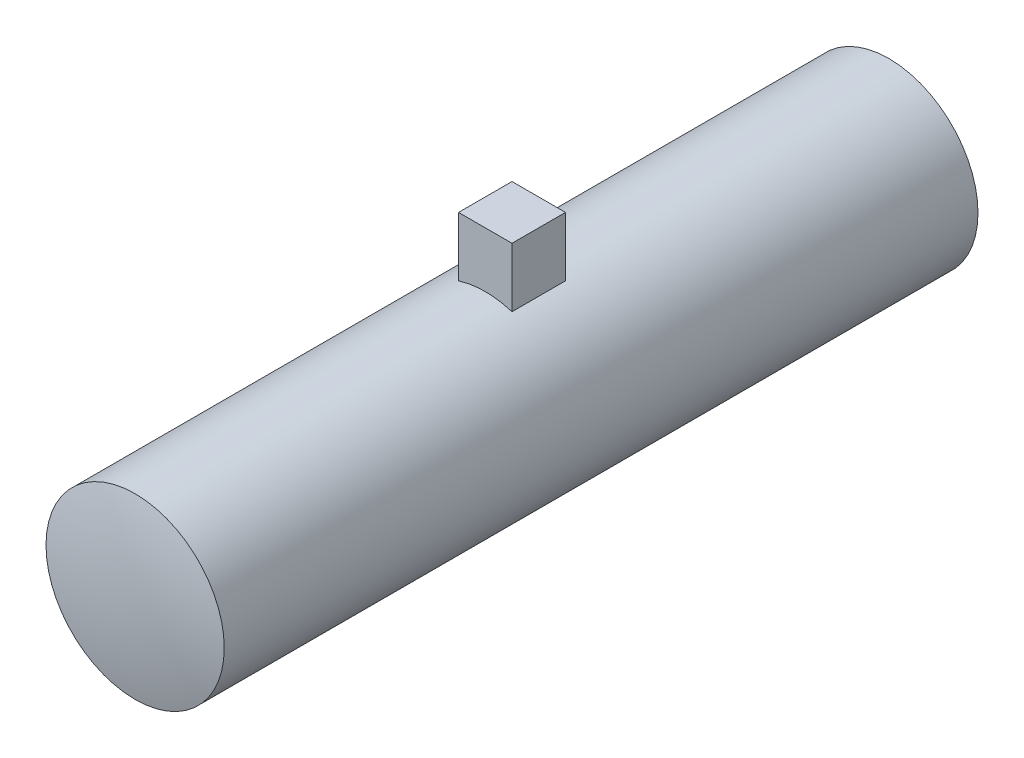
SolidWorks part; units mm, degrees
ref_plane "Front Plane" through (0, 0, 0) normal (0, 0, 1) x (1, 0, 0)
ref_plane "Top Plane" through (0, 0, 0) normal (0, 1, 0) x (1, 0, 0)
ref_plane "Right Plane" through (0, 0, 0) normal (1, 0, 0) x (0, 0, -1)
sketch "Sketch4" plane through (0, 0, 0) normal (0, 0, 1) x (1, 0, 0)
  line L0 (118.2783, 361.3249) -> (982.8327, 361.3249) construction
  line L1 (0, 0) -> (0, 70)
  line L2 (0, 70) -> (-2, 70)
  line L3 (-2, 70) -> (-2, 0)
  line L4 (-2, 0) -> (0, 0)
  line L5 (0, 0) -> (14, 0)
  line L6 (12.4732, 68.0138) -> (14.4732, 68.0138)
  line L7 (9, 0) -> (15, 0)
  line L8 (7, 0) -> (12.4732, 68.0138)
  line L10 (9, 0) -> (14.4732, 68.0138)
  line L11 (-2, 0) -> (-9, 0)
  line L12 (-9, 0) -> (-11, 0)
  line L13 (-11, 0) -> (-18, 0)
  line L14 (-18, 0) -> (-20, 0)
  line L15 (-11, 0) -> (-17.4559, 67.3971)
  line L16 (-17.4559, 67.3971) -> (-15.4559, 67.3971)
  line L17 (-15.4559, 67.3971) -> (-9, 0)
  line L18 (-18, 0) -> (-26.2108, 62.7795)
  line L19 (-26.2108, 62.7795) -> (-28.2108, 62.7795)
  line L20 (-28.2108, 62.7795) -> (-20, 0)
  line L21 (-20, 0) -> (-26, 0)
  line L22 (0, 65) -> (-20, 65)
  line L24 (0, 55) -> (20.8335, 55)
  line L26 (0, 50) -> (-31.2148, 50)
  line L27 (-26, 0) -> (15, 0)
  line L28 (-26, 0) -> (-26, -2)
  line L29 (-26, -2) -> (15, -2)
  line L30 (15, 0) -> (15, -2)
  dimension "D1" = 70
  dimension "D2" = 2
  dimension "D3" = 14
  dimension "D4" = 2
  dimension "D5" = 2
  dimension "D6" = 7
  dimension "D7" = 2
  dimension "D8" = 7
  dimension "D9" = 2
  dimension "D10" = 2
  dimension "D11" = 2
  dimension "D12" = 70
  dimension "D13" = 65
  dimension "D14" = 10
  dimension "D15" = 5
  dimension "D16" = 6
  dimension "D17" = 6
  dimension "D18" = 2
extrude "Boss-Extrude1" add sketch "Sketch4" along normal blind 2 contours L24 L8 L5 L10 | L1 L26 L3 L4 | L17 L26 L15 L12 | L18 L26 L20 L14 | L30 L7 L5 L4 L11 L12 L13 L14 L21 L28 L29 | L26 L17 L22 L15 | L26 L1 L22 L3 region at (-1, 25, 0) region at (-5.5, -1, 0) region at (-1, 57.5, 0) region at (10.213, 27.5, 0) region at (-12.3947, 25, 0) region at (-15.5079, 57.5, 0) region at (-22.2697, 25, 0)
sketch "Sketch5" plane through (0, 0, 2) normal (0, 0, 1) x (1, 0, 0)
  line L0 (7, 0) -> (11.4117, 54.8228)
  line L1 (7, 0) -> (11.426, 55) construction
  line L2 (11.4117, 54.8228) -> (21.9246, 53.9768)
  line L3 (9, 0) -> (13.3988, 54.6629)
  line L4 (9, 0) -> (13.426, 55) construction
  line L5 (-2, 0) -> (-2, 65)
  line L6 (-2, 65) -> (0, 65)
  line L7 (0, 65) -> (0, 0)
  line L8 (-9, 0) -> (-15.1979, 64.7038)
  line L9 (-15.2263, 65) -> (-9, 0) construction
  line L10 (-15.1979, 64.7038) -> (-10.585, 65.1457)
  line L11 (-24.4842, 49.5778) -> (-21.0999, 50.0204)
  line L12 (-10.585, 65.1457) -> (-20.2054, 64.2242)
  line L13 (-11, 0) -> (-17.1797, 64.514)
  line L14 (-11, 0) -> (-17.2263, 65) construction
  line L15 (-18, 0) -> (-24.4842, 49.5778)
  line L16 (-18, 0) -> (-24.5394, 50) construction
  line L17 (-21.0999, 50.0204) -> (-29.0833, 48.9763)
  line L18 (-20, 0) -> (-26.4506, 49.3206)
  line L20 (-24.4842, 55.6866) -> (-21.0999, 50.0204)
  line L23 (11.4117, 54.8228) -> (9.3756, 55.8722)
  line L25 (22.6925, 57.6139) -> (21.9246, 53.9768)
  line L26 (-10.585, 65.1457) -> (2.5876, 67.2021)
  line L27 (2.5876, 67.2021) -> (9.3756, 55.8722)
  line L28 (22.6925, 57.6139) -> (5.5245, 72.3941)
  line L29 (5.5245, 72.3941) -> (-16.3252, 68.1044)
  line L30 (-29.0833, 48.9763) -> (-29.6656, 62.8492)
  line L31 (-29.6656, 62.8492) -> (-16.3252, 68.1044)
  line L32 (-20.2054, 64.2242) -> (-24.4842, 55.6866)
  dimension "D1" = 55
  dimension "D2" = 90
  dimension "D3" = 65
  dimension "D4" = 90
  dimension "D5" = 50
  dimension "D6" = 90
extrude "Cut-Extrude4" cut sketch "Sketch5" against normal blind 10 contours L32 L12 L16 L14 L13 L10 L26 L27 L23 L3 L1 L2 L25 L28 L29 L31 L30 L17 L20 L18 L11 | L3 L2 L26 L1 | L12 L13 L14 L16 | L17 L18 L20 region at (10.6564, 55.8573, 2)
sketch "Sketch6" plane through (0, 0, 2) normal (0, 0, 1) x (1, 0, 0)
  line L0 (-24.4842, 49.5778) -> (-22.6038, 35.2002)
  line L1 (-18, 0) -> (-24.4842, 49.5778) construction
  line L2 (-15.1979, 64.7038) -> (-13.8153, 50.2699)
  line L3 (-15.1979, 64.7038) -> (-9, 0) construction
  line L4 (-2, 65) -> (-2, 50.5)
  line L5 (-2, 65) -> (-2, 0) construction
  line L6 (11.4117, 54.8228) -> (10.2486, 40.3695)
  line L7 (7, 0) -> (11.4117, 54.8228) construction
  line L8 (10.2486, 40.3695) -> (13.4056, 40.1154)
  line L9 (13.4056, 40.1154) -> (14.5687, 54.5687)
  line L10 (14.5687, 54.5687) -> (11.4117, 54.8228)
  line L11 (-2, 50.5) -> (0, 50.5)
  line L12 (0, 0) -> (0, 65) construction
  line L13 (0, 50.5) -> (0, 65)
  line L14 (0, 65) -> (-2, 65)
  line L15 (-15.1979, 64.7038) -> (-17.1797, 64.514)
  line L16 (-17.1797, 64.514) -> (-15.8153, 50.2699)
  line L17 (-11, 0) -> (-17.1797, 64.514) construction
  line L18 (-13.8153, 50.2699) -> (-15.7971, 50.0801)
  line L19 (-15.7971, 50.0801) -> (-16.1419, 53.6796)
  line L20 (-22.6038, 35.2002) -> (-24.5702, 34.943)
  line L21 (-26.4506, 49.3206) -> (-20, 0) construction
  line L22 (-24.5702, 34.943) -> (-26.4506, 49.3206)
  line L23 (-26.4506, 49.3206) -> (-24.4842, 49.5778)
  line L24 (-24.5702, 34.943) -> (-22.6038, 35.2002)
  line L25 (-24.4842, 49.5778) -> (-26.4506, 49.3206)
  line L26 (-24.5702, 34.943) -> (-26.4506, 49.3206)
  line M5 (-9, 0) -> (-15.1979, 64.7038)
  line M6 (-15.1979, 64.7038) -> (-17.1797, 64.514)
  line M7 (-17.1797, 64.514) -> (-11, 0)
  line M9 (-18, 0) -> (-24.4842, 49.5778)
  line M10 (-24.4842, 49.5778) -> (-26.4506, 49.3206)
  line M11 (-26.4506, 49.3206) -> (-20, 0)
  line M17 (9, 0) -> (13.3988, 54.6629)
  line M18 (13.3988, 54.6629) -> (11.4117, 54.8228)
  line M19 (11.4117, 54.8228) -> (7, 0)
  line M21 (0, 0) -> (0, 65)
  line M22 (0, 65) -> (-2, 65)
  line M23 (-2, 65) -> (-2, 0)
  dimension "D1" = 14.5
  dimension "D2" = 14.5
  dimension "D3" = 14.5
  dimension "D4" = 14.5
extrude "Cut-Extrude5" cut sketch "Sketch6" against normal blind 10 contours L8 M19 M17 M18 | L11 M23 M21 M22 | L18 L16 M5 M6 M7 | L20 M9 M10 M11 region at (-24.5272, 42.2604, 2) region at (-15.4975, 57.3919, 2) region at (-1, 57.75, 2) region at (11.8237, 47.5162, 2)
sketch "Sketch7" plane through (0, 50.5, 0) normal (0, 1, 0) x (1, 0, 0)
  line L0 (-1, 0) -> (-1, -2)
  line L1 (-2, 0) -> (0, 0) construction
  line L2 (-2, -2) -> (0, -2) construction
  line L5 (-7.25, 5.25) -> (5.25, 5.25)
  line L6 (-7.25, 5.25) -> (-7.25, -7.25)
  line L7 (-7.25, -7.25) -> (5.25, -7.25)
  line L8 (5.25, 5.25) -> (5.25, -7.25)
  line L9 (-7.25, 5.25) -> (5.25, -7.25) construction
  line L10 (-7.25, -7.25) -> (5.25, 5.25) construction
  point P7 (-1, -1)
  line M3 (-2, 0) -> (-2, -2)
  line M4 (-2, -2) -> (0, -2)
  line M5 (0, -2) -> (0, 0)
  line M6 (0, 0) -> (-2, 0)
  dimension "D1" = 12.5
  dimension "D2" = 12.5
extrude "Boss-Extrude2" add sketch "Sketch7" along normal blind 2.5 contours L8 L5 L6 L7 M3 M6 M5 M4 | L0 M6 M3 M4 | L0 M6 M4 M5 region at (-0.5, 50.5, 1) region at (-1.5, 50.5, 1) region at (-1, 50.5, -5.0732)
sketch "Sketch8" plane through (3.2936, 40.9292, 0) normal (0.0802, 0.9968, 0) x (0.9968, -0.0802, 0)
  line L0 (12.9774, 0) -> (10.9774, 0)
  line L1 (6.9774, 0) -> (12.9774, 0)
  line L2 (6.9774, 0) -> (6.9774, -2)
  line L3 (6.9774, -2) -> (12.9774, -2)
  line L4 (12.9774, 0) -> (12.9774, -2)
  line L5 (10.9774, 0) -> (10.9774, -2)
  dimension "D1" = 6
  dimension "D2" = 2
extrude "Boss-Extrude3" add sketch "Sketch8" against normal blind 41.5 contours L0 L5 L3 L4 region at (15.2325, 39.9684, 1)
sketch "Sketch9" plane through (0, 0, 2) normal (0, 0, 1) x (1, 0, 0)
  line L0 (7, 0) -> (9, 0)
  line L1 (9, 0) -> (12.2357, 40.2096)
  line L2 (12.2357, 40.2096) -> (10.2486, 40.3695)
  line L3 (10.2486, 40.3695) -> (7, 0)
extrude "Cut-Extrude6" cut sketch "Sketch9" against normal blind 41.5
sketch "Sketch10" plane through (-4.8971, 51.1242, 0) normal (-0.0954, 0.9954, 0) x (0.9954, 0.0954, 0)
  line L0 (-14.959, -2) -> (-12.959, -2)
  line L1 (-8.959, 0) -> (-14.959, 0)
  line L2 (-8.959, 0) -> (-8.959, -2)
  line L3 (-8.959, -2) -> (-14.959, -2)
  line L4 (-14.959, 0) -> (-14.959, -2)
  line L5 (-12.959, -2) -> (-12.959, 0)
  dimension "D1" = 6
  dimension "D2" = 2
extrude "Boss-Extrude4" add sketch "Sketch10" against normal blind 50.5 contours L0 L5 L1 L4 region at (-18.7925, 49.7931, 1)
sketch "Sketch11" plane through (0, 0, 2) normal (0, 0, 1) x (1, 0, 0)
  line L0 (-11, 0) -> (-9, 0)
  line L1 (-9, 0) -> (-13.8153, 50.2699)
  line L2 (-13.8153, 50.2699) -> (-15.7971, 50.0801)
  line L3 (-15.7971, 50.0801) -> (-11, 0)
extrude "Cut-Extrude7" cut sketch "Sketch11" against normal blind 50.5
sketch "Sketch12" plane through (3.2936, 40.9292, 0) normal (0.0802, 0.9968, 0) x (0.9968, -0.0802, 0)
  line L0 (11.9774, 0) -> (11.9774, -2)
  line L1 (12.9774, 0) -> (10.9774, 0) construction
  line L2 (10.9774, -2) -> (12.9774, -2) construction
  line L4 (5.7274, 5.25) -> (18.2274, 5.25)
  line L5 (5.7274, 5.25) -> (5.7274, -7.25)
  line L6 (5.7274, -7.25) -> (18.2274, -7.25)
  line L7 (18.2274, 5.25) -> (18.2274, -7.25)
  line L8 (5.7274, 5.25) -> (18.2274, -7.25) construction
  line L9 (5.7274, -7.25) -> (18.2274, 5.25) construction
  point P6 (11.9774, -1)
  line M3 (12.9774, 0) -> (10.9774, 0)
  line M4 (10.9774, 0) -> (10.9774, -2)
  line M5 (10.9774, -2) -> (12.9774, -2)
  line M6 (12.9774, -2) -> (12.9774, 0)
  dimension "D1" = 12.5
  dimension "D2" = 12.5
extrude "Boss-Extrude5" add sketch "Sketch12" along normal blind 2.5 contours L7 L4 L5 L6 M3 M6 M5 M4 | L0 M3 M5 M6 | L0 M3 M4 M5 region at (15.7309, 39.9283, 1) region at (14.7341, 40.0085, 1) region at (15.2325, 39.9684, -5.0732)
sketch "Sketch13" plane through (0, 0, 2) normal (0, 0, 1) x (1, 0, 0)
  line L0 (-5.5, -2) -> (-5.5, 50.5)
  line L1 (-26, -2) -> (15, -2) construction
  line L2 (-7.25, 50.5) -> (5.25, 50.5) construction
  line L3 (-17.7971, 49.8885) -> (-17.6064, 47.8976)
  line L4 (-13.0183, 0) -> (-17.7971, 49.8885) construction
  line L5 (-19.788, 49.6978) -> (-19.6155, 47.8976)
  line L6 (-15.0275, 0) -> (-19.788, 49.6978) construction
  line L7 (-19.788, 49.6978) -> (-17.7971, 49.8885)
  line L8 (-17.6064, 47.8976) -> (-19.5973, 47.7069)
  line L9 (-19.5973, 47.7069) -> (-19.6379, 48.1311)
  line M3 (-13.0183, 0) -> (-17.7971, 49.8885)
  line M4 (-17.7971, 49.8885) -> (-19.788, 49.6978)
  line M5 (-19.788, 49.6978) -> (-15.0275, 0)
  dimension "D1" = 2
extrude "Cut-Extrude8" cut sketch "Sketch13" against normal blind 2.5 and the other way through all contours L8 L5 M3 M4 M5 region at (-18.6972, 48.7977, 2)
sketch "Sketch14" plane through (-4.7064, 49.1333, 0) normal (-0.0954, 0.9954, 0) x (0.9954, 0.0954, 0)
  line L0 (-13.959, 0) -> (-13.959, -2)
  line L1 (-14.959, 0) -> (-12.959, 0) construction
  line L2 (-14.959, -2) -> (-12.959, -2) construction
  line L4 (-20.209, 5.25) -> (-7.709, 5.25)
  line L5 (-20.209, 5.25) -> (-20.209, -7.25)
  line L6 (-20.209, -7.25) -> (-7.709, -7.25)
  line L7 (-7.709, 5.25) -> (-7.709, -7.25)
  line L8 (-20.209, 5.25) -> (-7.709, -7.25) construction
  line L9 (-20.209, -7.25) -> (-7.709, 5.25) construction
  point P6 (-13.959, -1)
  line M3 (-14.959, -2) -> (-12.959, -2)
  line M4 (-12.959, -2) -> (-12.959, 0)
  line M5 (-12.959, 0) -> (-14.959, 0)
  line M6 (-14.959, 0) -> (-14.959, -2)
  dimension "D1" = 12.5
  dimension "D2" = 12.5
extrude "Boss-Extrude6" add sketch "Sketch14" along normal blind 2.5 contours L0 M5 M3 M4 | L0 M5 M6 M3 | L7 L4 L5 L6 M3 M6 M5 M4 region at (-18.1041, 47.8499, 1) region at (-19.0995, 47.7546, 1) region at (-18.6018, 47.8022, -5.0732)
sketch "Sketch15" plane through (-4.9065, 37.5148, 0) normal (-0.1297, 0.9916, 0) x (0.9916, 0.1297, 0)
  line L0 (-25.848, -2) -> (-23.848, -2)
  line L1 (-17.848, 0) -> (-25.848, 0)
  line L2 (-17.848, 0) -> (-17.848, -2)
  line L3 (-17.848, -2) -> (-25.848, -2)
  line L4 (-25.848, 0) -> (-25.848, -2)
  line L5 (-23.848, -2) -> (-23.848, 0)
  line L6 (-31.848, -2) -> (-29.848, -2)
  line L7 (-25.848, 0) -> (-31.848, 0)
  line L8 (-25.848, 0) -> (-25.848, -2)
  line L9 (-25.848, -2) -> (-31.848, -2)
  line L10 (-31.848, 0) -> (-31.848, -2)
  line L11 (-29.848, -2) -> (-29.848, 0)
  dimension "D1" = 8
  dimension "D2" = 2
  dimension "D3" = 6
  dimension "D4" = 2
extrude "Boss-Extrude7" add sketch "Sketch15" against normal blind 39.5 separate body contours L6 L11 L7 L10 region at (-35.494, 33.5143, 1)
sketch "Sketch16" plane through (-4.9065, 37.5148, 0) normal (-0.1297, 0.9916, 0) x (0.9916, 0.1297, 0)
  line L0 (-30.848, 0) -> (-30.848, -2)
  line L1 (-29.848, 0) -> (-31.848, 0) construction
  line L2 (-31.848, -2) -> (-29.848, -2) construction
  line L4 (-37.098, 5.25) -> (-24.598, 5.25)
  line L5 (-37.098, 5.25) -> (-37.098, -7.25)
  line L6 (-37.098, -7.25) -> (-24.598, -7.25)
  line L7 (-24.598, 5.25) -> (-24.598, -7.25)
  line L8 (-37.098, 5.25) -> (-24.598, -7.25) construction
  line L9 (-37.098, -7.25) -> (-24.598, 5.25) construction
  point P6 (-30.848, -1)
  line M3 (-31.848, -2) -> (-29.848, -2)
  line M4 (-29.848, -2) -> (-29.848, 0)
  line M5 (-29.848, 0) -> (-31.848, 0)
  line M6 (-31.848, 0) -> (-31.848, -2)
  dimension "D1" = 12.5
  dimension "D2" = 12.5
extrude "Boss-Extrude8" add sketch "Sketch16" along normal blind 2.5 contours L7 L4 L5 L6 M3 M6 M5 M4 | L0 M5 M3 M4 | L0 M5 M6 M3 region at (-34.9982, 33.5792, 1) region at (-35.9898, 33.4495, 1) region at (-35.494, 33.5143, -5.0732)
sketch "Sketch17" plane through (-5.2307, 39.9937, 0) normal (-0.1297, 0.9916, 0) x (0.9916, 0.1297, 0)
  line L0 (-37.098, -7.25) -> (-35.098, -7.25)
  line L1 (-37.098, 5.25) -> (-22.598, 5.25)
  line L2 (-37.098, 5.25) -> (-37.098, -7.25)
  line L3 (-37.098, -7.25) -> (-22.598, -7.25)
  line L4 (-22.598, 5.25) -> (-22.598, -7.25)
  line L5 (-35.098, -7.25) -> (-35.098, 5.25)
  line M2 (-24.598, -7.25) -> (-24.598, 5.25)
  dimension "D1" = 14.5
  dimension "D2" = 2
extrude "Boss-Extrude9" add sketch "Sketch17" against normal blind 2.5 contours L4 L1 L3 M2 region at (-28.6294, 36.9334, 1)
sketch "Sketch18" plane through (-5.2307, 39.9937, 0) normal (-0.1297, 0.9916, 0) x (0.9916, 0.1297, 0)
  line L0 (-37.098, -7.25) -> (-35.098, -7.25)
  line L2 (-35.098, -7.25) -> (-37.098, -7.25)
  line L3 (-35.098, -7.25) -> (-35.098, 5.25)
  line L4 (-35.098, 5.25) -> (-37.098, 5.25)
  line L5 (-37.098, -7.25) -> (-37.098, 5.25)
  line M2 (-37.098, -7.25) -> (-22.598, -7.25)
  line M4 (-22.598, 5.25) -> (-37.098, 5.25)
  line M5 (-37.098, 5.25) -> (-37.098, -7.25)
  dimension "D1" = 2
extrude "Cut-Extrude9" cut sketch "Sketch18" against normal blind 13.5 contours L3 M2 M4 M5 region at (-41.0239, 35.3124, 1)
sketch "Sketch19" plane through (-26, 0, 0) normal (-1, 0, 0) x (0, 0, 1)
  line L1 (0, 0) -> (2, 0)
  line L2 (0, 0) -> (0, -2)
  line L3 (0, -2) -> (2, -2)
  line L4 (2, 0) -> (2, -2)
extrude "Boss-Extrude10" add sketch "Sketch19" along normal blind 7.5
sketch "Sketch20" plane through (0, 0, 2) normal (0, 0, 1) x (1, 0, 0)
  line L0 (-31.8577, -2) -> (-29.8406, -2)
  line L1 (-29.8406, -2) -> (-29.3799, -5.5224)
  line L2 (-29.3799, -5.5224) -> (-31.363, -5.7818)
  line L3 (-31.363, -5.7818) -> (-31.8577, -2)
  line L4 (-20, 0) -> (-18, 0)
  line L5 (-18, 0) -> (-22.6038, 35.2002)
  line L6 (-22.6038, 35.2002) -> (-24.5702, 34.943)
  line L7 (-24.5702, 34.943) -> (-20, 0)
extrude "Cut-Extrude11" cut sketch "Sketch20" against normal blind 33.5
sketch "Sketch21" plane through (0, 0, 2) normal (0, 0, 1) x (1, 0, 0)
  line L0 (-36.4856, 33.3846) -> (-34.5025, 33.644)
  line L1 (-34.5025, 33.644) -> (-30.1022, 0)
  line L2 (-30.1022, 0) -> (-32.1192, 0)
  line L3 (-32.1192, 0) -> (-36.4856, 33.3846)
extrude "Cut-Extrude12" cut sketch "Sketch21" against normal blind 33.5
sketch "Sketch22" plane through (-4.9065, 37.5148, 0) normal (0.1297, -0.9916, 0) x (-0.9916, -0.1297, 0)
  line L0 (28.848, -7.25) -> (28.848, 5.25)
  line L1 (35.098, -7.25) -> (22.598, -7.25) construction
  line L2 (35.098, 5.25) -> (22.598, 5.25) construction
  line L3 (28.848, -1) -> (27.848, -1)
  line L4 (28.848, -1) -> (29.848, -1)
  line L5 (28.848, -1) -> (28.848, -2)
  line L6 (28.848, -1) -> (28.848, 0)
  line L8 (29.848, -1) -> (27.848, -1)
  line L9 (29.848, -1) -> (29.848, -2)
  line L10 (29.848, -2) -> (27.848, -2)
  line L11 (27.848, -1) -> (27.848, -2)
  line L12 (27.848, -1) -> (29.848, -1)
  line L13 (27.848, -1) -> (27.848, 0)
  line L14 (27.848, 0) -> (29.848, 0)
  line L15 (29.848, -1) -> (29.848, 0)
  dimension "D1" = 1
  dimension "D2" = 1
  dimension "D3" = 1
  dimension "D4" = 1
extrude "Boss-Extrude11" add sketch "Sketch22" along normal blind 35.5 contours L4 L15 L14 L0 | L10 L9 L4 L0 | L3 L11 L10 L0 | L14 L13 L3 L0 region at (-33.0151, 33.8385, 1.5) region at (-34.0067, 33.7088, 1.5) region at (-33.0151, 33.8385, 0.5) region at (-34.0067, 33.7088, 0.5)
sketch "Sketch24" plane through (18.1687, -1.4621, 0) normal (0.9968, -0.0802, 0) x (0, 0, -1)
  line L0 (-1, 41.0615) -> (-1, 55.5615)
  line L1 (5.25, 41.0615) -> (-7.25, 41.0615) construction
  line L2 (-1.7404, 43.5615) -> (-1.7404, 55.5615)
  line L3 (-7.25, 41.0615) -> (-1, 41.0615)
  line L4 (-7.25, 41.0615) -> (-7.25, 55.5615)
  line L6 (-1, 41.0615) -> (-1, 55.5615)
  line L8 (-1, 55.5615) -> (-1, 41.0615)
  line L9 (-1, 41.0615) -> (5.25, 41.0615)
  line L10 (5.25, 55.5615) -> (5.25, 41.0615)
  line L11 (5.25, 43.5615) -> (-7.25, 43.5615) construction
  line L12 (-7.25, 49.5615) -> (5.25, 49.5615)
  arc A1 (-7.25, 49.5615) -> (5.25, 49.5615) centre (-1, 49.282) cw
  point P17 (-1, 49.5615)
  line M4 (5.25, 43.5615) -> (-7.25, 43.5615)
  dimension "D1" = 14.5
extrude "Boss-Extrude13" add sketch "Sketch24" against normal blind 4 contours A1 L8 L12 | A1 L2 L12 L8 | A1 L12 L2 | L12 L4 L2 M4 | L12 L0 L10 M4 | L12 L2 L0 M4 region at (21.9035, 44.9494, 1.3702) region at (21.9035, 44.9494, -2.125) region at (22.3833, 50.9112, 1.3698) region at (22.3469, 50.459, -1.6268) region at (21.9035, 44.9494, 4.4952) region at (22.3404, 50.3778, 4.0322)
sketch "Sketch25" plane through (5.25, 0, 0) normal (1, 0, 0) x (0, 0, -1)
  line L0 (-1, 50.5) -> (-1, 65)
  line L1 (5.25, 50.5) -> (-7.25, 50.5) construction
  line L3 (-1, 65) -> (-7.25, 65)
  line L4 (-1, 65) -> (-1, 50.5)
  line L5 (-1, 50.5) -> (-7.25, 50.5)
  line L6 (-7.25, 65) -> (-7.25, 50.5)
  line L7 (-1, 65) -> (5.25, 65)
  line L8 (-1, 65) -> (-1, 50.5)
  line L9 (-1, 50.5) -> (5.25, 50.5)
  line L10 (5.25, 65) -> (5.25, 50.5)
  arc A0 (5.25, 57.75) -> (-7.25, 57.75) centre (-1, 58.681) ccw
  line M4 (5.25, 53) -> (-7.25, 53)
  dimension "D1" = 14.5
extrude "Boss-Extrude14" add sketch "Sketch25" against normal blind 4 contours L10 A0 L0 M4 | L0 A0 L6 M4 region at (5.25, 58.4301, 3.915) region at (5.25, 58.4301, -1.915)
sketch "Sketch26" plane through (-7.6739, -0.7351, 0) normal (0.9954, 0.0954, 0) x (0, 0, -1)
  line L0 (-1, 49.3582) -> (-1, 63.8582)
  line L1 (5.25, 49.3582) -> (-7.25, 49.3582) construction
  line L3 (-1, 63.8582) -> (-7.25, 63.8582)
  line L4 (-1, 63.8582) -> (-1, 49.3582)
  line L5 (-1, 49.3582) -> (-7.25, 49.3582)
  line L6 (-7.25, 63.8582) -> (-7.25, 49.3582)
  line L7 (-1, 63.8582) -> (5.25, 63.8582)
  line L8 (-1, 63.8582) -> (-1, 49.3582)
  line L9 (-1, 49.3582) -> (5.25, 49.3582)
  line L10 (5.25, 63.8582) -> (5.25, 49.3582)
  arc A0 (5.25, 56.6082) -> (-7.25, 56.6082) centre (-1, 57.5392) ccw
  line M4 (5.25, 51.8582) -> (-7.25, 51.8582)
  dimension "D1" = 14.5
extrude "Boss-Extrude15" add sketch "Sketch26" against normal blind 4 contours L10 A0 L0 M4 | L0 A0 L6 M4 region at (-13.1365, 56.2922, 3.915) region at (-13.1365, 56.2922, -1.915)
sketch "Sketch27" plane through (-22.4072, -2.9306, 0) normal (0.9916, 0.1297, 0) x (0, 0, -1)
  line L0 (-1, 37.8343) -> (-1, 52.3343)
  line L1 (5.25, 37.8343) -> (-7.25, 37.8343) construction
  line L3 (-1, 52.3343) -> (5.25, 52.3343)
  line L4 (-1, 52.3343) -> (-1, 37.8343)
  line L5 (-1, 37.8343) -> (5.25, 37.8343)
  line L6 (5.25, 52.3343) -> (5.25, 37.8343)
  line L7 (-1, 52.3343) -> (-7.25, 52.3343)
  line L8 (-1, 52.3343) -> (-1, 37.8343)
  line L9 (-1, 37.8343) -> (-7.25, 37.8343)
  line L10 (-7.25, 52.3343) -> (-7.25, 37.8343)
  arc A0 (5.25, 45.0843) -> (-7.25, 45.0843) centre (-1, 46.0153) ccw
  line M2 (5.25, 40.3343) -> (-7.25, 40.3343)
  dimension "D1" = 14.5
extrude "Boss-Extrude16" add sketch "Sketch27" against normal blind 4 contours L6 A0 L0 M2 | L0 A0 L10 M2 region at (-28.3421, 42.4474, 3.915) region at (-28.3421, 42.4474, -1.915)
sketch "Sketch28" plane through (0, 50.5, 0) normal (0, -1, 0) x (-1, 0, 0)
  line L0 (1, -2) -> (1, -7.25)
  line L1 (2, -2) -> (0, -2) construction
  line L2 (7.25, -7.25) -> (-5.25, -7.25) construction
  line L3 (1, -7.25) -> (1, 5.25)
  line L4 (7.25, 5.25) -> (-5.25, 5.25) construction
  circle A0 centre (1, -1) radius 4.5
  line M1 (2, 0) -> (2, -2)
  line M2 (2, -2) -> (0, -2)
  line M3 (0, -2) -> (0, 0)
  line M4 (0, 0) -> (2, 0)
  dimension "D1" = 9
extrude "Boss-Extrude17" add sketch "Sketch28" along normal blind 57 contours L3 A0 L0 M2 M3 M4 | L0 A0 L3 M4 M1 M2 region at (-3.0045, 50.5, 1) region at (1.0045, 50.5, 1)
sketch "Sketch29" plane through (-4.7064, 49.1333, 0) normal (0.0954, -0.9954, 0) x (-0.9954, -0.0954, 0)
  line L0 (13.959, -7.25) -> (13.959, 5.25)
  line L1 (20.209, -7.25) -> (7.709, -7.25) construction
  line L2 (20.209, 5.25) -> (7.709, 5.25) construction
  circle A0 centre (13.959, -1) radius 4.5
  line M1 (14.959, 0) -> (14.959, -2)
  line M2 (14.959, -2) -> (12.959, -2)
  line M3 (12.959, -2) -> (12.959, 0)
  line M4 (12.959, 0) -> (14.959, 0)
  dimension "D1" = 9
extrude "Boss-Extrude18" add sketch "Sketch29" along normal blind 57 contours L0 A0 M4 M1 M2 | L0 A0 M2 M3 M4 region at (-16.6065, 47.9934, 1) region at (-20.5971, 47.6111, 1)
sketch "Sketch30" plane through (-4.9065, 37.5148, 0) normal (0.1297, -0.9916, 0) x (0.9916, 0.1297, 0)
  line L0 (-28.848, 7.25) -> (-28.848, -5.25)
  line L1 (-35.098, 7.25) -> (-22.598, 7.25) construction
  line L2 (-35.098, -5.25) -> (-22.598, -5.25) construction
  circle A0 centre (-28.848, 1) radius 4.5
  line M1 (-27.848, 2) -> (-27.848, 0)
  line M2 (-27.848, 0) -> (-29.848, 0)
  line M3 (-29.848, 0) -> (-29.848, 2)
  line M4 (-29.848, 2) -> (-27.848, 2)
  dimension "D1" = 9
extrude "Boss-Extrude19" add sketch "Sketch30" along normal blind 57 contours L0 A0 M2 M3 M4 | L0 A0 M4 M1 M2 region at (-31.5234, 34.0336, 1) region at (-35.4984, 33.5137, 1)
sketch "Sketch31" plane through (3.2936, 40.9292, 0) normal (-0.0802, -0.9968, 0) x (-0.9968, 0.0802, 0)
  line L0 (-11.9774, -7.25) -> (-11.9774, 5.25)
  line L1 (-5.7274, -7.25) -> (-18.2274, -7.25) construction
  line L2 (-5.7274, 5.25) -> (-18.2274, 5.25) construction
  circle A0 centre (-11.9774, -1) radius 4.5
  line M5 (-10.9774, -2) -> (-12.9774, -2)
  line M6 (-12.9774, -2) -> (-12.9774, 0)
  line M7 (-12.9774, 0) -> (-10.9774, 0)
  line M8 (-10.9774, 0) -> (-10.9774, -2)
  dimension "D1" = 9
extrude "Boss-Extrude20" add sketch "Sketch31" along normal blind 57 contours L0 A0 M7 M8 M5 | L0 A0 M5 M6 M7 region at (17.2305, 39.8077, 1) region at (13.2345, 40.1292, 1)
sketch "Sketch32" plane through (0, -2, 0) normal (0, -1, 0) x (1, 0, 0)
  line L1 (-81.5094, 22.199) -> (41.4502, 22.199)
  line L2 (-81.5094, 22.199) -> (-81.5094, -20.6146)
  line L3 (-81.5094, -20.6146) -> (41.4502, -20.6146)
  line L4 (41.4502, 22.199) -> (41.4502, -20.6146)
  line L5 (-81.5094, 22.199) -> (41.4502, -20.6146) construction
  line L6 (-81.5094, -20.6146) -> (41.4502, 22.199) construction
  point P0 (-20.0296, 0.7922)
extrude "Cut-Extrude13" cut sketch "Sketch32" along normal blind 57
sketch "Sketch33" plane through (0, -2, 0) normal (0, -1, 0) x (-1, 0, 0)
  line L0 (24.4073, 0) -> (-7.4536, 0)
  line L1 (-7.4536, -2) -> (24.4073, -2)
  line L2 (8.4769, -2) -> (8.4769, 0)
  line L4 (30.9769, -9) -> (-14.0231, -9)
  line L5 (35.9769, -4) -> (35.9769, 2)
  line L6 (30.9769, 7) -> (-14.0231, 7)
  line L7 (-19.0231, -4) -> (-19.0231, 2)
  line L8 (35.9769, -9) -> (-19.0231, 7) construction
  line L9 (35.9769, 7) -> (-19.0231, -9) construction
  arc A0 (-19.0231, -4) -> (-14.0231, -9) centre (-14.0231, -4) ccw
  arc A1 (35.9769, -4) -> (30.9769, -9) centre (30.9769, -4) cw
  arc A2 (35.9769, 2) -> (30.9769, 7) centre (30.9769, 2) ccw
  arc A3 (-19.0231, 2) -> (-14.0231, 7) centre (-14.0231, 2) cw
  point P10 (8.4769, -1)
  line M1 (-3.3875, 0) -> (-7.4536, 0)
  ellipse M2 centre (-11.8552, -1) end of major axis (-16.3698, -1) minor radius 4.5 (-7.4536, 0) -> (-7.4536, -2) ccw
  line M3 (-7.4536, -2) -> (-3.3875, -2)
  arc M4 (-3.3875, -2) -> (5.3875, -2) centre (1, -1) ccw
  line M5 (5.3875, -2) -> (9.4237, -2)
  ellipse M6 centre (13.8313, -1) end of major axis (18.3519, -1) minor radius 4.5 (9.4237, -2) -> (18.2389, -2) ccw
  line M7 (18.2389, -2) -> (24.4073, -2)
  ellipse M8 centre (28.8321, -1) end of major axis (33.3704, -1) minor radius 4.5 (24.4073, -2) -> (33.257, -2) ccw
  line M9 (33.257, -2) -> (33.5, -2)
  line M10 (33.5, -2) -> (33.5, 0)
  line M11 (33.5, 0) -> (33.257, 0)
  ellipse M12 centre (28.8321, -1) end of major axis (33.3704, -1) minor radius 4.5 (33.257, 0) -> (24.4073, 0) ccw
  line M13 (24.4073, 0) -> (18.2389, 0)
  ellipse M14 centre (13.8313, -1) end of major axis (18.3519, -1) minor radius 4.5 (18.2389, 0) -> (9.4237, 0) ccw
  line M15 (9.4237, 0) -> (5.3875, 0)
  arc M16 (5.3875, 0) -> (-3.3875, 0) centre (1, -1) ccw
  dimension "D3" = 5
  dimension "D1" = 55
  dimension "D2" = 16
extrude "Boss-Extrude21" add sketch "Sketch33" along normal blind 1 contours A3 L7 A0 L4 A1 L5 A2 L6 L0 L1 M1 M16 M15 M14 M13 M12 M11 M10 M9 M8 M7 M6 M5 M4 M3 M2 | L2 L0 L1 M5 M1 M2 M3 | L2 L1 L0 M7 M8 M9 M10 M11 M12 M13 M15 | L1 M6 | L0 M14 | L0 M16 | L1 M4 region at (-24.7515, -2, 1) region at (-13.8313, -2, -1.4604) region at (7.7175, -2, 1) region at (-1, -2, -1.4606) region at (-1, -2, 3.4606) region at (-13.8313, -2, 3.4604) region at (-8.4769, -2, 8.4272)
sketch "Sketch34" plane through (-26.3734, -3.4493, 0) normal (-0.9916, -0.1297, 0) x (0, 0, 1)
  line L0 (1, 40.3343) -> (1, 46.9343)
  line L1 (-5.25, 40.3343) -> (7.25, 40.3343) construction
  circle A0 centre (1, 46.9343) radius 1.5
  dimension "D2" = 3
  dimension "D1" = 6.6
extrude "Cut-Extrude14" cut sketch "Sketch34" against normal blind 8 contours A0 region at (-32.3264, 42.0667, 2.0307)
sketch "Sketch35" plane through (-11.6556, -1.1165, 0) normal (-0.9954, -0.0954, 0) x (0, 0, 1)
  line L0 (1, 51.8582) -> (1, 58.4582)
  line L1 (-5.25, 51.8582) -> (7.25, 51.8582) construction
  circle A0 centre (1, 58.4582) radius 1.5
  dimension "D2" = 3
  dimension "D1" = 6.6
extrude "Cut-Extrude15" cut sketch "Sketch35" against normal blind 8 contours A0 region at (-17.1315, 56.0494, 2.0307)
sketch "Sketch36" plane through (1.25, 0, 0) normal (-1, 0, 0) x (0, 0, 1)
  line L0 (1, 53) -> (1, 59.6)
  line L1 (-5.25, 53) -> (7.25, 53) construction
  circle A0 centre (1, 59.6) radius 1.5
  dimension "D2" = 3
  dimension "D1" = 6.6
extrude "Cut-Extrude16" cut sketch "Sketch36" against normal blind 8 contours A0 region at (1.25, 58.5693, 2.0307)
sketch "Sketch37" plane through (14.1816, -1.1412, 0) normal (-0.9968, 0.0802, 0) x (0, 0, 1)
  line L0 (1, 43.5615) -> (1, 50.1615)
  line L1 (-5.25, 43.5615) -> (7.25, 43.5615) construction
  circle A0 centre (1, 50.1615) radius 1.5
  dimension "D2" = 3
  dimension "D1" = 6.6
extrude "Cut-Extrude17" cut sketch "Sketch37" against normal blind 8 contours A0 region at (18.1225, 47.8313, 2.0307)
sketch "Sketch38" plane through (0, -3, 0) normal (0, -1, 0) x (-1, 0, 0)
  line L0 (-19.0231, -4) -> (-19.0231, 2) construction
  line L1 (-19.0231, -1) -> (7.4808, -1)
  line L2 (-19.0231, -1) -> (-19.0231, -11)
  line L3 (-14.0231, -16) -> (7.4808, -16)
  line L4 (7.4808, -1) -> (7.4808, -16)
  line L5 (35.9769, -4) -> (35.9769, 2) construction
  line L6 (35.9769, -1) -> (7.4808, -1)
  line L7 (35.9769, -1) -> (35.9769, -11)
  line L8 (30.9769, -16) -> (7.4808, -16)
  line L9 (7.4808, -1) -> (7.4808, -16)
  arc A0 (30.9769, -16) -> (35.9769, -11) centre (30.9769, -11) ccw
  arc A1 (-14.0231, -16) -> (-19.0231, -11) centre (-14.0231, -11) cw
  point P14 (-19.0231, -16)
  arc M4 (-19.0231, -4) -> (-14.0231, -9) centre (-14.0231, -4) ccw
  line M5 (-14.0231, -9) -> (30.9769, -9)
  arc M6 (30.9769, -9) -> (35.9769, -4) centre (30.9769, -4) ccw
  dimension "D2" = 5
  dimension "D1" = 15
extrude "Boss-Extrude22" add sketch "Sketch38" against normal blind 1 contours A1 L3 L4 L2 M5 M4 | L8 A0 L7 L4 M6 M5 region at (5.7712, -3, 12.2976) region at (-21.7288, -3, 12.3117)
sketch "Sketch39" plane through (0, -2, 0) normal (0, 1, 0) x (1, 0, 0)
  line L0 (-34.5124, -14.5355) -> (-30.093, -18.955)
  line L1 (-38.9318, -10.1161) -> (-30.093, -18.955)
  line L2 (-38.9318, -10.1161) -> (-47.7706, -18.955)
  line L3 (-47.7706, -18.955) -> (-39.1652, -28.0271)
  line L4 (-39.1652, -28.0271) -> (-30.093, -18.955)
  arc A0 (-35.9769, -11) -> (-30.9769, -16) centre (-30.9769, -11) ccw construction
  point P7 (-34.5124, -14.5355)
  dimension "D1" = 6.25
  dimension "D2" = 12.5
extrude "Boss-Extrude23" add sketch "Sketch39" along normal blind 2 and the other way blind 2 separate body contours L3 L4 L0 L1 L2 region at (-38.9712, -2, 19.0327)
sketch "Sketch40" plane through (0, 0, 0) normal (0, 1, 0) x (1, 0, 0)
  line L0 (-38.9318, -10.1161) -> (-50.2455, -21.4298)
  line L1 (-30.093, -18.955) -> (-41.4067, -30.2687)
  line L2 (-38.9318, -10.1161) -> (-35.9769, -8.8888)
  line L3 (-35.9769, -11) -> (-35.9769, 2) construction
  line L4 (-35.9769, -8.8888) -> (-30.1971, -14.6685)
  line L5 (-35.9769, -8.8888) -> (-28.8656, -16)
  line L6 (14.0231, -16) -> (-30.9769, -16) construction
  line L7 (-28.8656, -16) -> (-30.093, -18.955)
  line L8 (-50.2455, -21.4298) -> (-41.4067, -30.2687)
  line M4 (-47.7706, -18.955) -> (-39.1652, -28.0271)
  line M6 (-30.093, -18.955) -> (-38.9318, -10.1161)
  dimension "D1" = 16
  dimension "D2" = 16
  dimension "D3" = 90
extrude "Boss-Extrude24" add sketch "Sketch40" against normal blind 4 contours L7 L5 L4 L2 M6 | L0 L8 L1 M4 region at (-33.5046, 0, 13.5277) region at (-44.7189, 0, 24.5963)
sketch "Sketch41" plane through (0, -2, 0) normal (0, 1, 0) x (1, 0, 0)
  line L0 (-41.4067, -30.2687) -> (-32.5678, -21.4298)
  line L1 (-41.4067, -30.2687) -> (-30.093, -18.955) construction
  line L2 (-50.2455, -21.4298) -> (-41.4067, -12.591)
  line L3 (-38.9318, -10.1161) -> (-50.2455, -21.4298) construction
  line L4 (-41.4067, -12.591) -> (-32.5678, -21.4298)
  line L5 (-50.2455, -21.4298) -> (-41.4067, -30.2687)
  line L6 (-32.5678, -21.4298) -> (-35.3963, -18.6014)
  line L7 (-35.3963, -18.6014) -> (-44.2351, -27.4402)
  dimension "D1" = 12.5
  dimension "D2" = 12.5
  dimension "D3" = 4
extrude "Boss-Extrude25" add sketch "Sketch41" along normal blind 12.5 contours L4 L7 L5 L0 region at (-38.4015, -2, 24.435)
sketch "Sketch42" plane through (-8.3974, 0, -8.3974) normal (-0.7071, 0, -0.7071) x (-0.7071, 0, 0.7071)
  line L0 (50.6821, 10.5) -> (50.6821, 0) construction
  line L1 (38.1821, 10.5) -> (38.1821, 0) construction
  arc A0 (50.6821, 5.25) -> (38.1821, 5.25) centre (44.4321, 4.1548) ccw
  arc A1 (38.1821, 5.25) -> (50.6821, 5.25) centre (44.4321, 9.3395) cw
extrude "Cut-Extrude18" cut sketch "Sketch42" against normal blind 12.5
sketch "Sketch43" plane through (-14.4078, 0, -14.4078) normal (-0.7071, 0, -0.7071) x (-0.7071, 0, 0.7071)
  line L0 (50.6821, -4) -> (50.6821, 0)
  line L3 (50.6821, -2) -> (34.6821, -2)
  line L4 (50.6821, -2) -> (50.6821, 0)
  line L5 (50.6821, 0) -> (34.6821, 0)
  line L6 (34.6821, -2) -> (34.6821, 0)
  point P3 (50.6821, -2)
  line M3 (50.6821, 0) -> (34.6821, 0)
  line M4 (34.6821, 0) -> (34.6821, -4)
extrude "Cut-Extrude19" cut sketch "Sketch43" against normal blind 8.5 contours L3 L0 M3 M4 region at (-44.5887, -1, 15.773)
sketch "Sketch44" plane through (-8.3974, 0, -8.3974) normal (-0.7071, 0, -0.7071) x (-0.7071, 0, 0.7071)
  line L0 (44.4321, 10.5) -> (44.4321, -2)
  line L1 (50.6821, -2) -> (34.6821, -2) construction
  line L2 (44.4321, -2) -> (44.4321, 4.6)
  arc A0 (50.6821, 5.25) -> (38.1821, 5.25) centre (44.4321, 4.1548) ccw construction
  circle A1 centre (44.4321, 4.6) radius 1.5
  dimension "D2" = 3
  dimension "D1" = 6.6
extrude "Cut-Extrude20" cut sketch "Sketch44" against normal blind 8.5 contours L0 A1 | L0 A1 region at (-40.2658, 4.6, 23.471) region at (-39.3655, 4.6, 22.5707)
sketch "Sketch45" plane through (0, -3, 0) normal (0, -1, 0) x (-1, 0, 0)
  line L0 (7.4212, -16) -> (7.4212, 7)
  line L1 (-14.0231, -16) -> (28.8656, -16) construction
  line L2 (30.9769, 7) -> (-14.0231, 7) construction
  line L3 (8.4769, 7) -> (8.4769, -16)
  circle A0 centre (8.4769, -4.5) radius 9
  dimension "D1" = 18
extrude "Boss-Extrude27" add sketch "Sketch45" along normal blind 20 contours L0 A0 | L3 A0 L0 | L3 A0 region at (-4.0807, -3, 4.5) region at (-7.9496, -3, 4.5) region at (-12.2966, -3, 4.5)
sketch "Sketch46" plane through (0, 0, 0) normal (0, 0, 1) x (1, 0, 0)
  line L3 (-8.4769, -45.8264) -> (-8.4769, -89.2893)
  arc A1 (-8.4769, -45.8264) -> (-8.4769, -89.2893) centre (-8.4769, -67.5578) cw
revolve "Revolve1" add sketch "Sketch46" angle 360 about L3
sketch "Sketch47" plane through (0, -23, 0) normal (0, -1, 0) x (-1, 0, 0)
  circle A0 centre (8.4769, -4.5) radius 9
sketch "Sketch50" plane through (0, 0, 0) normal (0, 1, 0) x (1, 0, 0)
  line L0 (-8.4769, 21.7314) -> (-8.4769, -21.7314)
  circle A0 centre (-8.4769, 0) radius 21.7314 construction
  circle A1 centre (-8.4769, 0) radius 9
  dimension "D1" = 18
extrude "Cut-Extrude23" cut sketch "Sketch50" against normal blind 65 from offset 30 contours L0 A1 | L0 A1 region at (-4.6571, 0, 0) region at (-12.2966, 0, 0) offset against normal yes
sketch "Sketch52" plane through (0, 0, 0) normal (1, 0, 0) x (0, 0, -1)
  line L0 (0, -47.7777) -> (0, -87.338)
  line L1 (9, -47.7777) -> (-9, -47.7777) construction
  line L2 (-9, -87.338) -> (9, -87.338) construction
  line L3 (0, -87.338) -> (0, -67.5578)
  line L5 (10.1618, -87.338) -> (-10.1618, -87.338)
  line L6 (10.1618, -87.338) -> (10.1618, -47.7777)
  line L7 (10.1618, -47.7777) -> (-10.1618, -47.7777)
  line L8 (-10.1618, -87.338) -> (-10.1618, -47.7777)
  line L9 (10.1618, -87.338) -> (-10.1618, -47.7777) construction
  line L10 (10.1618, -47.7777) -> (-10.1618, -87.338) construction
  line L11 (28.3288, -45.1895) -> (-28.3288, -45.1895)
  line L12 (28.3288, -45.1895) -> (28.3288, -89.9262)
  line L13 (28.3288, -89.9262) -> (-28.3288, -89.9262)
  line L14 (-28.3288, -45.1895) -> (-28.3288, -89.9262)
  line L15 (28.3288, -45.1895) -> (-28.3288, -89.9262) construction
  line L16 (28.3288, -89.9262) -> (-28.3288, -45.1895) construction
extrude "Cut-Extrude24" cut sketch "Sketch52" against normal blind 65 and the other way blind 65 contours L11 L14 L13 L12 L5 L8 L7 L6 region at (0, -67.5578, -27.6069)
sketch "Sketch53" plane through (0, 0, 0) normal (0, 1, 0) x (1, 0, 0)
  line L1 (-8.8004, -28.9281) -> (-8.8004, -72.3881)
  arc A3 (-8.8004, -72.3881) -> (-8.8004, -28.9281) centre (-8.8004, -50.6581) cw
revolve "Revolve2" add sketch "Sketch53" angle 360 about L1
sketch "Sketch54" plane through (0, 0, 0) normal (0, 1, 0) x (1, 0, 0)
  line L0 (-8.8004, -72.3881) -> (-8.8004, -49.9784)
  line L1 (-8.8004, -72.3881) -> (1.3596, -72.3881)
  line L2 (-20.1024, -72.3881) -> (2.5017, -72.3881)
  line L3 (-20.1024, -72.3881) -> (-20.1024, -28.9281)
  line L4 (-20.1024, -28.9281) -> (2.5017, -28.9281)
  line L5 (2.5017, -72.3881) -> (2.5017, -28.9281)
  line L6 (-20.1024, -72.3881) -> (2.5017, -28.9281) construction
  line L7 (-20.1024, -28.9281) -> (2.5017, -72.3881) construction
  line L8 (-18.9604, -72.3881) -> (1.3596, -72.3881)
  line L10 (1.3596, -72.3881) -> (-18.9604, -72.3881)
  line L11 (1.3596, -72.3881) -> (1.3596, -28.9281)
  line L12 (1.3596, -28.9281) -> (-18.9604, -28.9281)
  line L13 (-18.9604, -72.3881) -> (-18.9604, -28.9281)
  circle A0 centre (-8.8004, -50.6581) radius 21.73 construction
  circle A1 centre (-8.8004, -50.6581) radius 21.73
  point P14 (-8.8004, -72.3881)
  dimension "D1" = 22.6041
  dimension "D2" = 10.16
extrude "Cut-Extrude25" cut sketch "Sketch54" against normal blind 65 and the other way blind 65 contours L11 A1 L13 region at (-13.9189, 0, 71.2826)
sketch "Sketch55" plane through (0, 0, 0) normal (0, 0, 1) x (1, 0, 0)
  line L2 (67.524, -43.8258) -> (67.524, -0.3658)
  arc A3 (67.524, -0.3658) -> (67.524, -43.8258) centre (67.524, -22.0958) ccw
revolve "Revolve3" add sketch "Sketch55" angle 360 about L2
sketch "Sketch56" plane through (0, 0, 0) normal (0, 0, 1) x (1, 0, 0)
  circle A0 centre (67.524, -22.0958) radius 5
  circle A1 centre (67.524, -22.0958) radius 43.6141
  dimension "D1" = 10
extrude "Cut-Extrude26" cut sketch "Sketch56" against normal blind 68 and the other way blind 65
sketch "Sketch57" plane through (0, 0, 10.1618) normal (0, 0, 1) x (1, 0, 0)
  circle A0 centre (-8.4769, -67.5578) radius 5
  dimension "D1" = 10
extrude "Cut-Extrude27" cut sketch "Sketch57" against normal blind 65
sketch "Sketch58" plane through (0, 0, 0) normal (1, 0, 0) x (0, 0, -1)
  circle A0 centre (-50.6581, 0) radius 5
  dimension "D1" = 10
extrude "Cut-Extrude28" cut sketch "Sketch58" against normal blind 38 and the other way blind 17
sketch "Sketch59" plane through (0, 0, 10.1618) normal (0, 0, 1) x (1, 0, 0)
  line L0 (-8.4769, -67.5578) -> (10.7323, -67.5578)
  line L1 (-8.4769, -67.5578) -> (-27.686, -67.5578)
  line L2 (-14.7269, -61.3078) -> (-2.2269, -61.3078)
  line L3 (-14.7269, -61.3078) -> (-14.7269, -73.8078)
  line L4 (-14.7269, -73.8078) -> (-2.2269, -73.8078)
  line L5 (-2.2269, -61.3078) -> (-2.2269, -73.8078)
  line L6 (-14.7269, -61.3078) -> (-2.2269, -73.8078) construction
  line L7 (-14.7269, -73.8078) -> (-2.2269, -61.3078) construction
  line L8 (23.0587, -67.5578) -> (-40.0124, -67.5578)
  line L9 (-40.0124, -40.1199) -> (23.0587, -40.1199)
  line L10 (-40.0124, -40.1199) -> (-40.0124, -94.9958)
  line L11 (-40.0124, -94.9958) -> (23.0587, -94.9958)
  line L12 (23.0587, -40.1199) -> (23.0587, -94.9958)
  line L13 (-40.0124, -40.1199) -> (23.0587, -94.9958) construction
  line L14 (-40.0124, -94.9958) -> (23.0587, -40.1199) construction
  circle A0 centre (-8.4769, -67.5578) radius 19.2092 construction
  circle M4 centre (-8.4769, -67.5578) radius 19.2092
  dimension "D1" = 12.5
  dimension "D2" = 12.5
extrude "Cut-Extrude29" cut sketch "Sketch59" against normal blind 38 contours L12 L8 L10 L11 M4 | L0 L5 L4 L3 L1 M4 region at (-8.4769, -76.4937, 10.1618) region at (16.8955, -68.2457, 10.1618)
sketch "Sketch60" plane through (-18.9604, 0, 0) normal (1, 0, 0) x (0, 0, -1)
  line L0 (-50.6581, -5) -> (-50.6581, 5)
  line L1 (-26.7055, 0) -> (-74.6107, 0)
  line L2 (-26.7055, 24.8261) -> (-74.6107, 24.8261)
  line L3 (-56.9081, 6.25) -> (-44.4081, 6.25)
  line L4 (-56.9081, 6.25) -> (-56.9081, -6.25)
  line L5 (-56.9081, -6.25) -> (-44.4081, -6.25)
  line L6 (-44.4081, 6.25) -> (-44.4081, -6.25)
  line L7 (-56.9081, 6.25) -> (-44.4081, -6.25) construction
  line L8 (-56.9081, -6.25) -> (-44.4081, 6.25) construction
  line L9 (-26.7055, 24.8261) -> (-26.7055, -24.8261)
  line L10 (-26.7055, -24.8261) -> (-74.6107, -24.8261)
  line L11 (-74.6107, 24.8261) -> (-74.6107, -24.8261)
  line L12 (-26.7055, 24.8261) -> (-74.6107, -24.8261) construction
  line L13 (-26.7055, -24.8261) -> (-74.6107, 24.8261) construction
  circle A1 centre (-50.6581, 0) radius 5 construction
  point P7 (-50.6581, 0)
  point P8 (-50.6581, 0)
  point P18 (-50.6581, 0)
  circle M4 centre (-50.6581, 0) radius 19.2085
  dimension "D1" = 12.5
  dimension "D2" = 12.5
extrude "Cut-Extrude30" cut sketch "Sketch60" against normal blind 38 and the other way blind 38 contours L1 L6 L5 L4 M4 | L1 L11 L10 L9 M4 region at (-18.9604, -12.413, 27.245) region at (-18.9604, -8.9356, 50.6581)
sketch "Sketch61" plane through (0, 0, 0) normal (0, 0, 1) x (1, 0, 0)
  line L1 (-56.142, 69.5548) -> (36.856, 69.5548)
  line L2 (-56.142, 69.5548) -> (-56.142, -34.6971)
  line L3 (-56.142, -34.6971) -> (36.856, -34.6971)
  line L4 (36.856, 69.5548) -> (36.856, -34.6971)
  line L5 (36.856, 69.5548) -> (88.781, 69.5548)
  line L6 (36.856, 69.5548) -> (36.856, -60.2112)
  line L7 (36.856, -60.2112) -> (88.781, -60.2112)
  line L8 (88.781, 69.5548) -> (88.781, -60.2112)
  line L9 (-56.142, -34.6971) -> (31.1223, -34.6971)
  line L10 (-56.142, -34.6971) -> (-56.142, -105.6449)
  line L11 (-56.142, -105.6449) -> (31.1223, -105.6449)
  line L12 (31.1223, -34.6971) -> (31.1223, -105.6449)
extrude "Cut-Extrude36" cut sketch "Sketch61" against normal blind 38 and the other way blind 79 contours L12 L3 L10 L11 | L4 L1 L2 L3 region at (-9.643, 17.4288, 0) region at (-12.5099, -70.171, 0)
sketch "Sketch62" plane through (0, 0, 0) normal (0, 1, 0) x (1, 0, 0)
  line L0 (67.524, 21.1469) -> (67.524, -21.1469)
  line L1 (72.524, 21.1469) -> (62.524, 21.1469) construction
  line L2 (62.524, -21.1469) -> (72.524, -21.1469) construction
  line L4 (66.024, 1.5) -> (69.024, 1.5)
  line L5 (66.024, 1.5) -> (66.024, -1.5)
  line L6 (66.024, -1.5) -> (69.024, -1.5)
  line L7 (69.024, 1.5) -> (69.024, -1.5)
  line L8 (66.024, 1.5) -> (69.024, -1.5) construction
  line L9 (66.024, -1.5) -> (69.024, 1.5) construction
  point P6 (67.524, 0)
  dimension "D1" = 3
  dimension "D2" = 3
extrude "Boss-Extrude28" add sketch "Sketch62" along normal blind 6 from offset 20 contours L7 L4 L0 L6 | L5 L6 L0 L4 region at (68.274, 0, 0) region at (66.774, 0, 0) offset against normal yes
